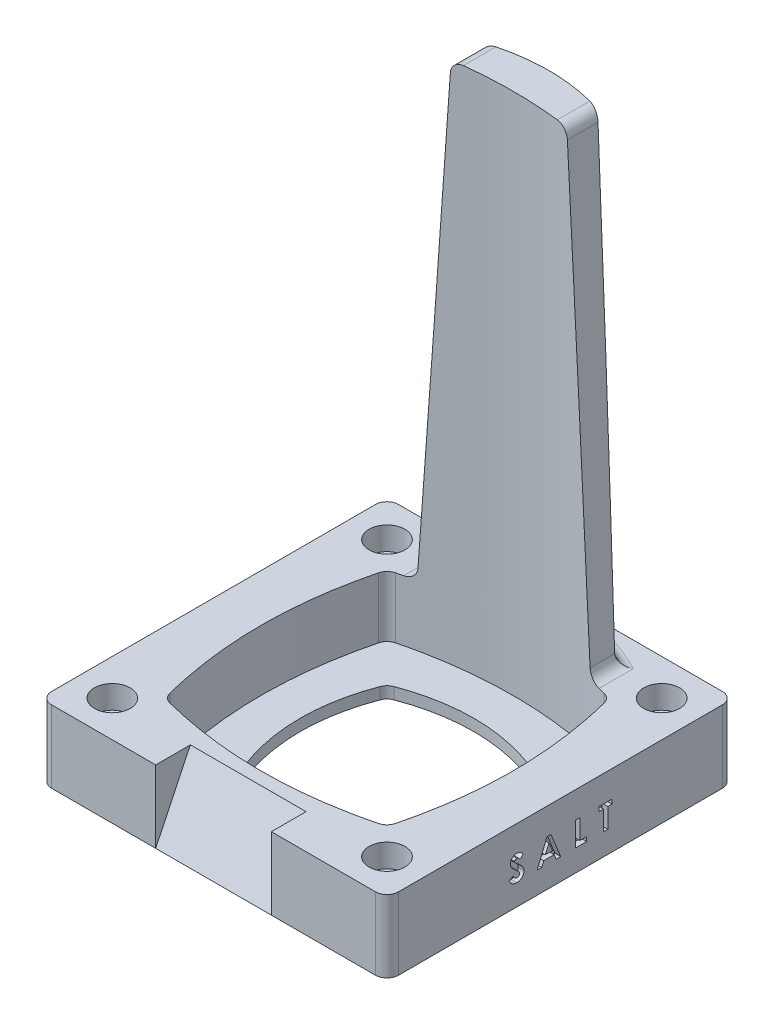
SolidWorks part; units mm, degrees
ref_plane "Front Plane" through (0, 0, 0) normal (0, 0, 1) x (1, 0, 0)
ref_plane "Top Plane" through (0, 0, 0) normal (0, 1, 0) x (1, 0, 0)
ref_plane "Right Plane" through (0, 0, 0) normal (1, 0, 0) x (0, 0, -1)
sketch "Sketch1" plane through (0, 0, 0) normal (0, 1, 0) x (1, 0, 0)
  line L1 (-38.1, -38.1) -> (38.1, -38.1)
  line L2 (-38.1, -38.1) -> (-38.1, 38.1)
  line L3 (-38.1, 38.1) -> (38.1, 38.1)
  line L4 (38.1, -38.1) -> (38.1, 38.1)
  line L5 (-38.1, -38.1) -> (38.1, 38.1) construction
  line L6 (-38.1, 38.1) -> (38.1, -38.1) construction
  point P0 (0, 0)
  dimension "D1" = 76.2
  dimension "D2" = 76.2
extrude "Boss-Extrude1" add sketch "Sketch1" along normal blind 15.875
sketch "Sketch2" plane through (0, 15.875, 0) normal (0, 1, 0) x (1, 0, 0)
  line L0 (-27.686, 0) -> (29.454, 0) construction
  line L1 (-24.384, -24.384) -> (24.384, -24.384) construction
  line L2 (-24.384, -24.384) -> (-24.384, 24.384) construction
  line L3 (-24.384, 24.384) -> (24.384, 24.384) construction
  line L4 (24.384, -24.384) -> (24.384, 24.384) construction
  line L5 (-24.384, -24.384) -> (24.384, 24.384) construction
  line L6 (-24.384, 24.384) -> (24.384, -24.384) construction
  line L7 (-27.686, -27.686) -> (27.686, -27.686) construction
  line L8 (-27.686, -27.686) -> (-27.686, 27.686) construction
  line L9 (-27.686, 27.686) -> (27.686, 27.686) construction
  line L10 (27.686, -27.686) -> (27.686, 27.686) construction
  line L11 (-27.686, -27.686) -> (27.686, 27.686) construction
  line L12 (-27.686, 27.686) -> (27.686, -27.686) construction
  line L13 (0, 27.686) -> (0, -27.686) construction
  spline S0 degree 2 poles (-24.384, 24.384) (-30.988, 0) (-24.384, -24.384) knots 0 0 0 1 1 1
  spline S1 degree 2 poles (-24.384, 24.384) (0, 30.988) (24.384, 24.384) knots 0 0 0 1 1 1
  spline S2 degree 2 poles (24.384, 24.384) (30.988, 0) (24.384, -24.384) knots 0 0 0 1 1 1
  spline S3 degree 2 poles (24.384, -24.384) (0, -30.988) (-24.384, -24.384) knots 0 0 0 1 1 1
  point P0 (0, 0)
  point P6 (0, 0)
  dimension "D1" = 48.768
  dimension "D2" = 48.768
  dimension "D3" = 55.372
  dimension "D4" = 55.372
extrude "Cut-Extrude1" cut sketch "Sketch2" against normal blind 13.335
sketch "Sketch4" plane through (0, 15.875, 0) normal (0, 1, 0) x (1, 0, 0)
  line L1 (-30.1625, -30.1625) -> (30.1625, -30.1625) construction
  line L2 (-30.1625, -30.1625) -> (-30.1625, 30.1625) construction
  line L3 (-30.1625, 30.1625) -> (30.1625, 30.1625) construction
  line L4 (30.1625, -30.1625) -> (30.1625, 30.1625) construction
  line L5 (-30.1625, -30.1625) -> (30.1625, 30.1625) construction
  line L6 (-30.1625, 30.1625) -> (30.1625, -30.1625) construction
  circle A0 centre (-30.1625, 30.1625) radius 2.54
  circle A1 centre (30.1625, 30.1625) radius 2.54
  circle A2 centre (30.1625, -30.1625) radius 2.54
  circle A3 centre (-30.1625, -30.1625) radius 2.54
  point P0 (0, 0)
  dimension "D3" = 5.08
  dimension "D4" = 5.08
  dimension "D5" = 5.08
  dimension "D6" = 5.08
  dimension "D1" = 60.325
  dimension "D2" = 60.325
extrude "Cut-Extrude3" cut sketch "Sketch4" against normal through all
fillet "Fillet2" radius 2.54 4 edges at (-38.1, 7.9375, 38.1) (38.1, 7.9375, 38.1) (38.1, 7.9375, -38.1) (-38.1, 7.9375, -38.1)
sketch "Sketch8" plane through (0, 2.54, 0) normal (0, 1, 0) x (1, 0, 0)
  line L0 (-19.05, 0) -> (29.3905, 0) construction
  line L1 (-15.875, -15.875) -> (15.875, -15.875) construction
  line L2 (-15.875, -15.875) -> (-15.875, 15.875) construction
  line L3 (-15.875, 15.875) -> (15.875, 15.875) construction
  line L4 (15.875, -15.875) -> (15.875, 15.875) construction
  line L5 (-15.875, -15.875) -> (15.875, 15.875) construction
  line L6 (-15.875, 15.875) -> (15.875, -15.875) construction
  line L7 (-19.05, -19.05) -> (19.05, -19.05) construction
  line L8 (-19.05, -19.05) -> (-19.05, 19.05) construction
  line L9 (-19.05, 19.05) -> (19.05, 19.05) construction
  line L10 (19.05, -19.05) -> (19.05, 19.05) construction
  line L11 (-19.05, -19.05) -> (19.05, 19.05) construction
  line L12 (-19.05, 19.05) -> (19.05, -19.05) construction
  line L13 (0, 19.05) -> (0, -19.05) construction
  spline S0 degree 2 poles (-15.875, 15.875) (-22.225, 0) (-15.875, -15.875) knots 0 0 0 1 1 1
  spline S1 degree 2 poles (-15.875, 15.875) (0, 22.225) (15.875, 15.875) knots 0 0 0 1 1 1
  spline S2 degree 2 poles (15.875, 15.875) (22.225, 0) (15.875, -15.875) knots 0 0 0 1 1 1
  spline S3 degree 2 poles (15.875, -15.875) (0, -22.225) (-15.875, -15.875) knots 0 0 0 1 1 1
  point P0 (0, 0)
  point P5 (0, 0)
  dimension "D1" = 38.1
  dimension "D2" = 31.75
  dimension "D3" = 31.75
  dimension "D4" = 38.1
  dimension "D5" = 0
  dimension "D6" = 0
extrude "Cut-Extrude4" cut sketch "Sketch8" against normal through all
fillet "Fillet3" radius 2.54 8 edges at (15.875, 1.27, -15.875) (15.875, 1.27, 15.875) (-15.875, 1.27, 15.875) (-15.875, 1.27, -15.875) (-24.384, 9.2075, -24.384) (-24.384, 9.2075, 24.384) (24.384, 9.2075, 24.384) (24.384, 9.2075, -24.384)
sketch "Sketch9" plane through (0, 15.875, 0) normal (0, 1, 0) x (1, 0, 0)
  line L0 (-26.67, 26.67) -> (-24.384, 24.384)
  line L1 (-27.686, -27.686) -> (27.686, -27.686) construction
  line L2 (-27.686, -27.686) -> (-27.686, 27.686) construction
  line L3 (-27.686, 27.686) -> (27.686, 27.686) construction
  line L4 (27.686, -27.686) -> (27.686, 27.686) construction
  line L5 (-27.686, -27.686) -> (27.686, 27.686) construction
  line L6 (-27.686, 27.686) -> (27.686, -27.686) construction
  line L7 (-24.384, -24.384) -> (24.384, -24.384) construction
  line L8 (-24.384, -24.384) -> (-24.384, 24.384) construction
  line L9 (-24.384, 24.384) -> (24.384, 24.384) construction
  line L10 (24.384, -24.384) -> (24.384, 24.384) construction
  line L11 (-24.384, -24.384) -> (24.384, 24.384) construction
  line L12 (-24.384, 24.384) -> (24.384, -24.384) construction
  line L13 (-30.48, -35.56) -> (30.48, -35.56) construction
  line L14 (-30.48, -35.56) -> (-30.48, 35.56) construction
  line L15 (-30.48, 35.56) -> (30.48, 35.56) construction
  line L16 (30.48, -35.56) -> (30.48, 35.56) construction
  line L17 (-30.48, -35.56) -> (30.48, 35.56) construction
  line L18 (-30.48, 35.56) -> (30.48, -35.56) construction
  line L19 (26.67, -26.67) -> (-26.67, -26.67) construction
  line L20 (26.67, -26.67) -> (26.67, 26.67) construction
  line L21 (26.67, 26.67) -> (-26.67, 26.67) construction
  line L22 (-26.67, -26.67) -> (-26.67, 26.67) construction
  line L23 (26.67, -26.67) -> (-26.67, 26.67) construction
  line L24 (26.67, 26.67) -> (-26.67, -26.67) construction
  line L25 (26.67, 26.67) -> (24.384, 24.384)
  spline S0 degree 2 poles (-24.384, 24.384) (0, 30.988) (24.384, 24.384) knots 0 0 0 1 1 1
  spline S1 degree 2 poles (-26.67, 26.67) (0, 44.45) (26.67, 26.67) knots 0 0 0 1 1 1
  point P0 (0, 0)
  point P6 (0, 0)
  point P12 (0, 0)
  point P17 (0, 0)
  dimension "D1" = 55.372
  dimension "D2" = 55.372
  dimension "D3" = 48.768
  dimension "D4" = 48.768
  dimension "D5" = 71.12
  dimension "D6" = 60.96
  dimension "D7" = 53.34
  dimension "D8" = 53.34
extrude "Boss-Extrude2" add sketch "Sketch9" along normal blind 101.6
sketch "Sketch10" plane through (0, 0, 0) normal (0, 0, 1) x (1, 0, 0)
  line L0 (0, 122.457) -> (0, 0) construction
  line L1 (-12.7, 117.475) -> (-19.05, 15.875)
  line L2 (24.384, 117.475) -> (-24.384, 117.475) construction
  line L3 (-35.56, 15.875) -> (35.56, 15.875) construction
  line L4 (12.7, 117.475) -> (19.05, 15.875)
  line L7 (-12.7, 117.475) -> (-26.67, 117.475)
  line L8 (-26.67, 117.475) -> (-26.67, 15.875)
  line L9 (-26.67, 15.875) -> (-19.05, 15.875)
  line L10 (12.7, 117.475) -> (26.67, 117.475)
  line L11 (26.67, 117.475) -> (26.67, 15.875)
  line L12 (26.67, 15.875) -> (19.05, 15.875)
  dimension "D1" = 12.7
  dimension "D2" = 19.05
extrude "Cut-Extrude5" cut sketch "Sketch10" against normal through all
fillet "Fillet4" radius 2.54 2 edges at (12.7, 117.475, -30.1672) (-12.7, 117.475, -30.1672)
sketch "Sketch11" plane through (0, 0, 0) normal (1, 0, 0) x (0, 0, -1)
  line L0 (-30.48, 15.875) -> (-38.1, 0)
  line L1 (35.56, 15.875) -> (-35.56, 15.875) construction
  line L2 (-38.1, 0) -> (-38.1, 15.875)
  line L3 (-38.1, 15.875) -> (-30.48, 15.875)
  dimension "D1" = 7.62
extrude "Cut-Extrude6" cut sketch "Sketch11" against normal mid plane 25.4
sketch "Sketch13" plane through (0, 15.875, 0) normal (0, 1, 0) x (1, 0, 0)
  circle A0 centre (30.1625, 30.1625) radius 3.937
  circle A1 centre (30.1625, -30.1625) radius 3.937
  circle A2 centre (-30.1625, -30.1625) radius 3.937
  circle A3 centre (-30.1625, 30.1625) radius 3.937
  dimension "D1" = 7.874
  dimension "D2" = 7.874
  dimension "D3" = 7.874
  dimension "D4" = 7.874
extrude "Cut-Extrude8" cut sketch "Sketch13" against normal blind 5.08
fillet "Fillet5" radius 2.54 3 edges at (19.05, 15.875, -28.3475) (-19.05, 15.875, -28.3475)
sketch "Sketch14" plane through (-38.1, 0, 0) normal (-1, 0, 0) x (0, 0, 1)
  line L0 (-35.56, 7.9375) -> (35.56, 7.9375) construction
  line L1 (-35.56, 15.875) -> (-35.56, 0) construction
  line L2 (35.56, 0) -> (35.56, 15.875) construction
  line L3 (-35.56, 4.7625) -> (35.56, 4.7625) construction
  text T0 "<b>SALT</b>" font "Century Gothic" height in points 20
  dimension "D1" = 3.175
extrude "Cut-Extrude9" cut sketch "Sketch14" against normal blind 1.27
sketch "Sketch15" plane through (38.1, 0, 0) normal (1, 0, 0) x (0, 0, -1)
  line L0 (-35.56, 4.7625) -> (35.56, 4.7625) construction
  line L1 (-35.56, 15.875) -> (-35.56, 0) construction
  line L2 (35.56, 0) -> (35.56, 15.875) construction
  text T0 "<b>SALT</b>" font "Century Gothic" height in points 20
  point P6 (-35.56, 7.9375)
  dimension "D1" = 3.175
extrude "Cut-Extrude10" cut sketch "Sketch15" against normal blind 1.27
